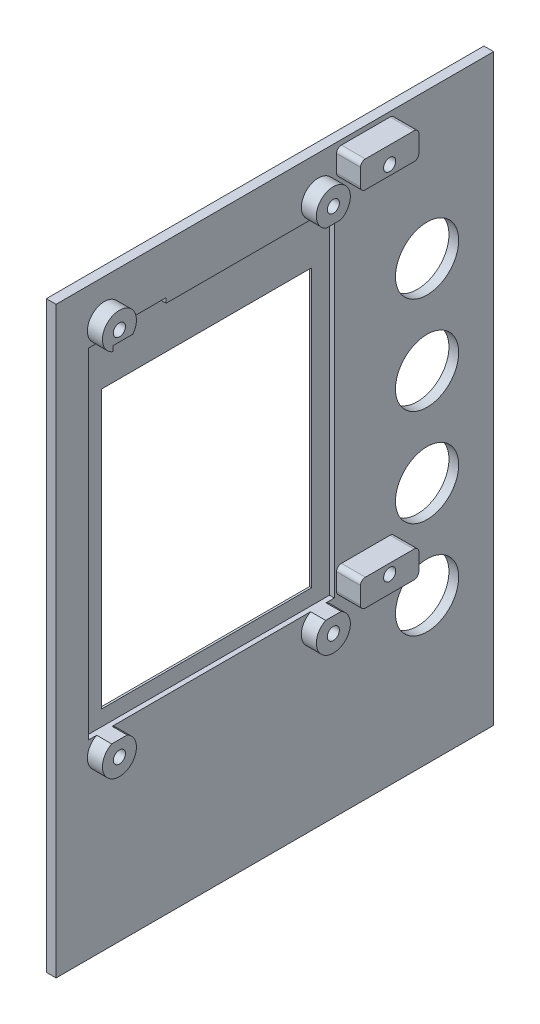
SolidWorks part; units mm, degrees
ref_plane "Front Plane" through (0, 0, 0) normal (0, 0, 1) x (1, 0, 0)
ref_plane "Top Plane" through (0, 0, 0) normal (0, 1, 0) x (1, 0, 0)
ref_plane "Right Plane" through (0, 0, 0) normal (1, 0, 0) x (0, 0, -1)
ref_plane "Plane2" through (-1175.0441, 0, 0) normal (-1, 0, 0) x (0, 0, 1)
sketch "Sketch2" plane through (-1175.0441, 0, 0) normal (-1, 0, 0) x (0, 0, 1)
  line L0 (-1293.9703, -887.0459) -> (-1293.9703, -787.0459) construction
  line L1 (-1208.9703, -777.0459) -> (-1298.9703, -777.0459)
  line L2 (-1208.9703, -777.0459) -> (-1208.9703, -897.0459)
  line L3 (-1208.9703, -897.0459) -> (-1298.9703, -897.0459)
  line L4 (-1298.9703, -777.0459) -> (-1298.9703, -897.0459)
  line L5 (-1293.9703, -887.0459) -> (-1292.4603, -887.0459) construction
  line L6 (-1293.9703, -787.0459) -> (-1292.4603, -787.0459) construction
  circle A0 centre (-1285.2753, -867.0459) radius 6.5
  circle A1 centre (-1285.2753, -847.0459) radius 6.5
  circle A2 centre (-1285.2753, -827.0459) radius 6.5
  circle A3 centre (-1285.2753, -807.0459) radius 6.5
  ellipse E0 centre (-1285.2753, -867.0459) end of major axis (-1284.8157, -867.5055) minor radius 0.65 construction
  ellipse E1 centre (-1285.2753, -847.0459) end of major axis (-1284.8157, -847.5055) minor radius 0.65 construction
  ellipse E2 centre (-1285.2753, -827.0459) end of major axis (-1284.8157, -827.5055) minor radius 0.65 construction
  ellipse E3 centre (-1285.2753, -807.0459) end of major axis (-1284.8157, -807.5055) minor radius 0.65 construction
  ellipse E4 centre (-1285.2753, -867.0459) end of major axis (-1284.8157, -867.5055) minor radius 0.65
  ellipse E5 centre (-1285.2753, -847.0459) end of major axis (-1284.8157, -847.5055) minor radius 0.65 construction
  ellipse E6 centre (-1285.2753, -827.0459) end of major axis (-1284.8157, -827.5055) minor radius 0.65
  ellipse E7 centre (-1285.2753, -807.0459) end of major axis (-1284.8157, -807.5055) minor radius 0.65
  dimension "D5" = 13
  dimension "D6" = 13
  dimension "D7" = 13
  dimension "D8" = 13
  dimension "D1" = 5
  dimension "D2" = 10
  dimension "D3" = 10
  dimension "D4" = 90
extrude "Boss-Extrude2" add sketch "Sketch2" along normal blind 2 contours L1 L4 L3 L2 A3 A2 A1 A0 region at (-1175.0441, -837.0459, -1252.3518)
sketch "Sketch3" plane through (-1177.0441, 0, 0) normal (-1, 0, 0) x (0, 0, 1)
  line L12 (-1219.3105, -854.8056) -> (-1262.5105, -854.8056) construction
  line L13 (-1262.5105, -854.8056) -> (-1262.5105, -797.8256) construction
  line L14 (-1219.3105, -797.8256) -> (-1219.3105, -854.8056) construction
  line L15 (-1262.5105, -797.8256) -> (-1219.3105, -797.8256) construction
  line L16 (-1219.3105, -854.8056) -> (-1262.5105, -854.8056)
  line L17 (-1262.5105, -854.8056) -> (-1262.5105, -797.8256)
  line L18 (-1219.3105, -797.8256) -> (-1219.3105, -854.8056)
  line L19 (-1262.5105, -797.8256) -> (-1219.3105, -797.8256)
extrude "tft_cutout" cut sketch "Sketch3" against normal through all
sketch "tft_inset_cutout" plane through (-1175.0441, 0, 0) normal (1, 0, 0) x (0, 0, -1)
  line L4 (1216.1105, -788.6846) -> (1216.1105, -857.4846) construction
  line L5 (1265.7105, -788.6846) -> (1216.1105, -788.6846) construction
  line L12 (1265.7105, -857.4846) -> (1265.7105, -788.6846) construction
  line L17 (1216.1105, -857.4846) -> (1265.7105, -857.4846) construction
  line L18 (1265.7105, -857.4846) -> (1265.7105, -788.6846) construction
  line L19 (1216.1105, -857.4846) -> (1265.7105, -857.4846) construction
  line L20 (1216.1105, -788.6846) -> (1216.1105, -857.4846) construction
  line L21 (1265.7105, -788.6846) -> (1216.1105, -788.6846) construction
  line L22 (1266.2105, -788.1846) -> (1215.6105, -788.1846)
  line L26 (1217.6105, -788.6846) -> (1231.6105, -788.6846)
  line L27 (1217.6105, -788.6846) -> (1217.6105, -787.1846)
  line L28 (1217.6105, -787.1846) -> (1231.6105, -787.1846)
  line L29 (1231.6105, -788.6846) -> (1231.6105, -787.1846)
  line L30 (1215.6105, -788.1846) -> (1215.6105, -857.9846)
  line L31 (1215.6105, -857.9846) -> (1266.2105, -857.9846)
  line L32 (1266.2105, -857.9846) -> (1266.2105, -788.1846)
  line M40 (1262.5105, -854.8056) -> (1219.3105, -854.8056)
  line M41 (1219.3105, -854.8056) -> (1219.3105, -797.8256)
  line M42 (1219.3105, -797.8256) -> (1262.5105, -797.8256)
  line M43 (1262.5105, -797.8256) -> (1262.5105, -854.8056)
  dimension "D3" = 1.5
  dimension "D4" = 0.5
  dimension "D1" = 14
  dimension "D2" = 1.5
extrude "Cut-Extrude2" cut sketch "tft_inset_cutout" against normal up to surface (1 mm away) contours L18 | L31 L32 L22 L29 L26 L27 L30 M43 M40 M41 M42 | L26 L29 L22 L27 | L22 L29 L28 L27 region at (-1175.0441, -823.0846, -1265.3484) region at (-1175.0441, -788.4346, -1224.6105) region at (-1175.0441, -787.6846, -1224.6105)
chamfer "Chamfer2" distance 1 angle 30 4 edges at (-1177.0441, -826.3156, -1262.5105) (-1177.0441, -854.8056, -1240.9105) (-1177.0441, -826.3156, -1219.3105) (-1177.0441, -797.8256, -1240.9105) first distance on face at (-1177.0441, -826.3156, -1240.9105)
sketch "Sketch6" plane through (-1175.0441, 0, 0) normal (1, 0, 0) x (0, 0, -1)
  line L5 (1266.6605, -858.0374) -> (1278.6605, -858.0374)
  line L6 (1266.6605, -858.0374) -> (1266.6605, -852.5374)
  line L7 (1266.6605, -852.5374) -> (1278.6605, -852.5374)
  line L8 (1266.6605, -858.0374) -> (1278.6605, -858.0374)
  line L9 (1278.6605, -858.0374) -> (1278.6605, -778.0374)
  line L10 (1278.6605, -778.0374) -> (1266.6605, -778.0374)
  line L11 (1266.6605, -778.0374) -> (1266.6605, -858.0374)
  line L12 (1266.6605, -858.0374) -> (1278.6605, -858.0374) construction
  line L13 (1278.6605, -858.0374) -> (1278.6605, -778.0374) construction
  line L14 (1278.6605, -778.0374) -> (1266.6605, -778.0374) construction
  line L15 (1266.6605, -778.0374) -> (1266.6605, -858.0374) construction
  line L16 (1278.6605, -858.0374) -> (1278.6605, -852.5374)
  line L17 (1266.6605, -778.0374) -> (1278.6605, -778.0374)
  line L18 (1266.6605, -778.0374) -> (1266.6605, -783.5374)
  line L19 (1266.6605, -783.5374) -> (1278.6605, -783.5374)
  line L20 (1278.6605, -778.0374) -> (1278.6605, -783.5374)
  circle A0 centre (1272.6605, -854.5374) radius 1.25 construction
  circle A1 centre (1272.6605, -854.5374) radius 1.25 construction
  circle A2 centre (1272.6605, -854.5374) radius 1.25
  circle A3 centre (1272.6605, -781.5374) radius 1.25 construction
  circle A4 centre (1272.6605, -781.5374) radius 1.25 construction
  circle A5 centre (1272.6605, -781.5374) radius 1.25
  dimension "D2" = 2.5
  dimension "D4" = 2.5
  dimension "D3" = 2
  dimension "D5" = 2
extrude "menu_standoffs" add sketch "Sketch6" along normal up to surface (4.9229 mm away)
fillet "Fillet1" radius 1 8 edges at (-1172.5827, -783.5374, -1266.6605) (-1172.5827, -783.5374, -1278.6605) (-1172.5827, -778.0374, -1278.6605) (-1172.5827, -778.0374, -1266.6605) (-1172.5827, -852.5374, -1278.6605) (-1172.5827, -852.5374, -1266.6605) (-1172.5827, -858.0374, -1266.6605) (-1172.5827, -858.0374, -1278.6605)
sketch "Sketch7" plane through (-1170.1212, 0, 0) normal (1, 0, 0) x (0, 0, -1)
  circle A0 centre (1272.6605, -854.5374) radius 1.25 construction
  circle A1 centre (1272.6605, -781.5374) radius 1.25 construction
  circle A2 centre (1272.6605, -854.5374) radius 1.25
  circle A3 centre (1272.6605, -781.5374) radius 1.25
extrude "menu_standoff_holes" cut sketch "Sketch7" against normal blind 5
sketch "Sketch8" plane through (-1175.0441, 0, 0) normal (1, 0, 0) x (0, 0, -1)
  circle A0 centre (1218.9105, -861.1056) radius 1.55 construction
  circle A1 centre (1262.9105, -861.1056) radius 1.55 construction
  circle A2 centre (1262.9105, -785.0256) radius 1.55 construction
  circle A3 centre (1218.9105, -785.0258) radius 1.55 construction
  circle A4 centre (1218.9105, -861.1056) radius 1.55 construction
  circle A5 centre (1262.9105, -861.1056) radius 1.55 construction
  circle A6 centre (1262.9105, -785.0256) radius 1.55 construction
  circle A7 centre (1218.9105, -785.0258) radius 1.55 construction
  circle A8 centre (1218.9105, -785.0258) radius 3.5
  circle A9 centre (1262.9105, -785.0256) radius 3.5
  circle A10 centre (1262.9105, -861.1056) radius 3.5
  circle A11 centre (1218.9105, -861.1056) radius 3.5
  circle A12 centre (1218.9105, -785.0258) radius 1.25
  circle A13 centre (1218.9105, -861.1056) radius 1.25
  circle A14 centre (1262.9105, -861.1056) radius 1.25
  circle A15 centre (1262.9105, -785.0256) radius 1.25
  dimension "D2" = 2.5
  dimension "D1" = 7
extrude "TFT_standoffs" add sketch "Sketch8" along normal up to surface (3.09 mm away)
sketch "Sketch9" plane through (-1175.0441, 0, 0) normal (1, 0, 0) x (0, 0, -1)
  circle A0 centre (1218.9105, -785.0258) radius 1.25 construction
  circle A1 centre (1218.9105, -861.1056) radius 1.25 construction
  circle A2 centre (1262.9105, -861.1056) radius 1.25 construction
  circle A3 centre (1262.9105, -785.0256) radius 1.25 construction
  circle A4 centre (1218.9105, -785.0258) radius 1.25
  circle A5 centre (1218.9105, -861.1056) radius 1.25
  circle A6 centre (1262.9105, -861.1056) radius 1.25
  circle A7 centre (1262.9105, -785.0256) radius 1.25
extrude "TFT_standoff_holes" cut sketch "Sketch9" against normal offset from surface (1 mm away) 1 up to face at (-1177.0441, -826.3156, -1240.9105)
extrude "Cut-Extrude5" cut sketch "Sketch5<3>" along normal through all contours L31 L32 L22 L29 L26 L27 L30 M43 M40 M41 M42 | L22 L29 L28 L27 | L26 L29 L22 L27 region at (-1175.0441, -823.0846, -1265.3484) region at (-1175.0441, -788.4346, -1224.6105) region at (-1175.0441, -787.6846, -1224.6105)
sketch "Sketch5<3>" plane through (-1175.0441, 0, 0) normal (1, 0, 0) x (0, 0, -1) same geometry as "tft_inset_cutout"
equation "\"R_BNC\"= 13"
equation "\"D8@Sketch2\"=\"R_BNC\""
equation "\"D7@Sketch2\"=\"R_BNC\""
equation "\"D6@Sketch2\"=\"R_BNC\""
equation "\"D5@Sketch2\"=\"R_BNC\""
equation "\"R_m3_TAP\"= 2.5"
equation "\"D2@Sketch6\"=\"R_m3_TAP\""
equation "\"D4@Sketch6\"=\"R_m3_TAP\""
equation "\"R_TFT_mount_outer\" = 7"
equation "\"D1@Sketch8\"=\"R_TFT_mount_outer\""
equation "\"D2@Sketch8\"=\"R_m3_TAP\""
